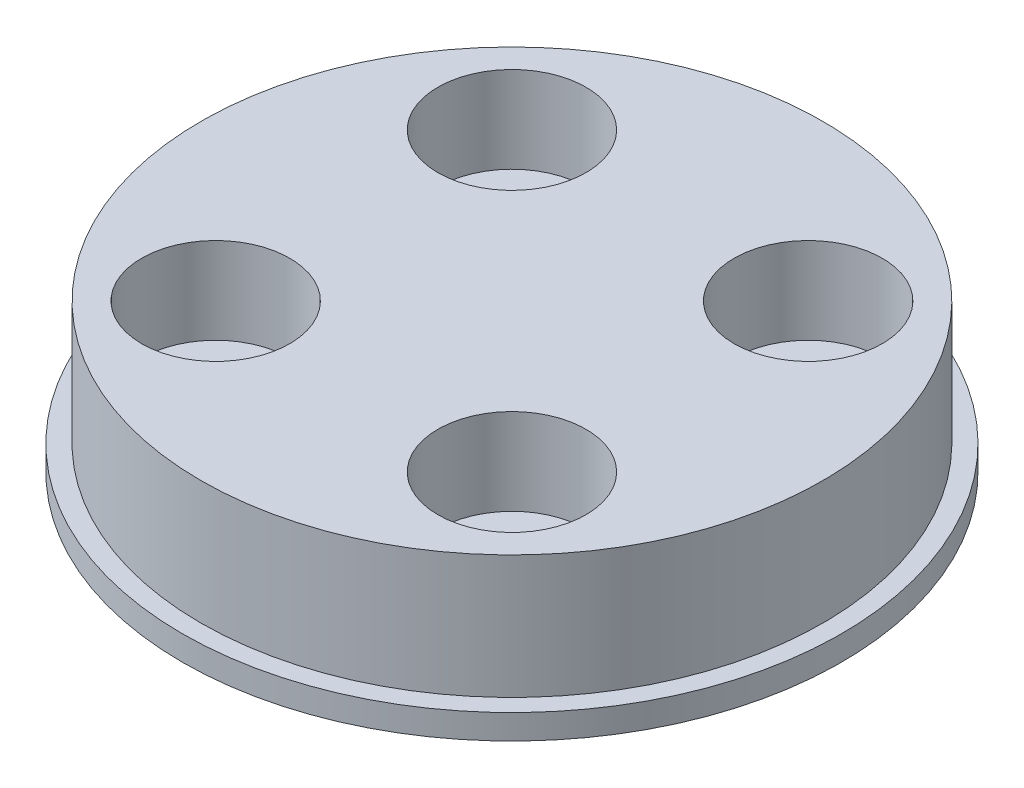
SolidWorks part; units mm, degrees
material "ABS"
ref_plane "Front Plane" through (0, 0, 0) normal (0, 0, 1) x (1, 0, 0)
ref_plane "Top Plane" through (0, 0, 0) normal (0, 1, 0) x (1, 0, 0)
ref_plane "Right Plane" through (0, 0, 0) normal (1, 0, 0) x (0, 0, -1)
sketch "Sketch1" plane through (0, 33, 0) normal (0, 1, 0) x (1, 0, 0)
  circle A0 centre (0, 0) radius 12.6
  circle A1 centre (0, 0) radius 13.35
  circle A2 centre (-6, 6) radius 1.575
  circle A3 centre (6, 6) radius 1.575
  circle A4 centre (6, -6) radius 1.575
  circle A5 centre (-6, -6) radius 1.575
  point P16 (0, 0)
  circle M2 centre (-6, -6) radius 1.575
  circle M3 centre (6, -6) radius 1.575
  circle M4 centre (6, 6) radius 1.575
  circle M5 centre (-6, 6) radius 1.575
  dimension "D1" = 3.15
  dimension "D3" = 25.2
  dimension "D4" = 26.7
  dimension "D2" = 4
extrude "Boss-Extrude1" add sketch "Sketch1" along normal blind 1 contours A0 M3 M5 M4 M2 | A1 A0 region at (0, 33, 0) region at (-12.9724, 33, 0)
extrude "Boss-Extrude2" add sketch "Sketch1<3>" along normal blind 6 contours A0 M3 M5 M4 M2 region at (0, 33, 0)
sketch "Sketch1<3>" plane through (0, 33, 0) normal (0, 1, 0) x (1, 0, 0) same geometry as "Sketch1"
sketch "Sketch2" plane through (0, 39, 0) normal (0, 1, 0) x (1, 0, 0)
  circle A0 centre (-6, 6) radius 3
  circle A1 centre (6, 6) radius 3
  circle A2 centre (6, -6) radius 3
  circle A3 centre (-6, -6) radius 3
  point P12 (0, 0)
  dimension "D1" = 6
  dimension "D2" = 4
extrude "Cut-Extrude1" cut sketch "Sketch2" against normal blind 3.5
equation "\"RingPinShaft\"= 5.05"
equation "\"CenterBearingOut\"=32.05"
equation "\"OutputBearingOut\"=37.05"
equation "\"RingPostIn\"=5.15"
equation "\"CamBearingOut\"=15.1"
equation "\"DiskOutputShaft\"=10.1"
equation "\"CenterShaft\"=25.2"
equation "\"Eccentricity\"=2"
equation "\"CycCamShaft\"=10.05"
equation "\"m3Thru\"=3.15"
equation "\"m3Insert\"=4.2"
equation "\"D1@Sketch1\"=\"m3Thru\""
equation "\"D3@Sketch1\"=\"CenterShaft\""
equation "\"D4@Sketch1\"=\"CenterShaft\"+1.5"
